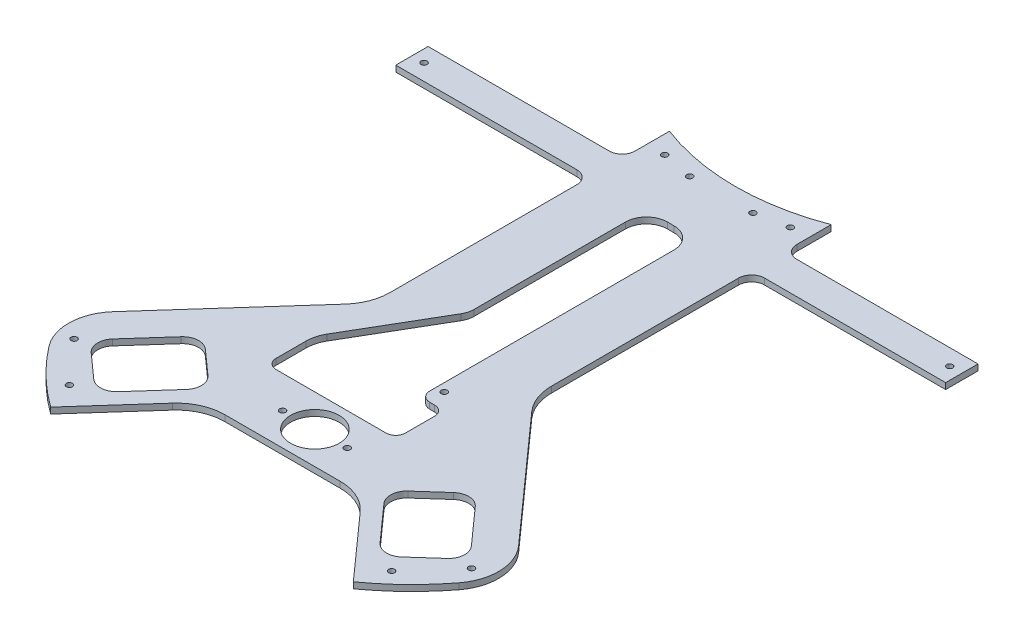
SolidWorks part; units mm, degrees
material "6063-T1"
ref_plane "Front Plane" through (0, 0, 0) normal (0, 0, 1) x (1, 0, 0)
ref_plane "Top Plane" through (0, 0, 0) normal (0, 1, 0) x (1, 0, 0)
ref_plane "Right Plane" through (0, 0, 0) normal (1, 0, 0) x (0, 0, -1)
sketch "Sketch1" plane through (0, 0, 0) normal (0, 1, 0) x (1, 0, 0)
  line L0 (-63.5, 31.75) -> (-178.5164, -97.0677)
  line L1 (-215.9, 31.75) -> (215.9, 31.75)
  line L2 (-215.9, 31.75) -> (-215.9, -31.75)
  line L3 (-215.9, -31.75) -> (215.9, -31.75)
  line L4 (215.9, 31.75) -> (215.9, -31.75)
  line L5 (-215.9, 31.75) -> (215.9, -31.75) construction
  line L6 (-215.9, -31.75) -> (215.9, 31.75) construction
  line L7 (63.5, 31.75) -> (-63.5, 31.75)
  line L8 (63.5, 31.75) -> (63.5, 292.608)
  line L9 (63.5, 292.608) -> (-63.5, 292.608)
  line L10 (-63.5, 31.75) -> (-63.5, 292.608)
  line L11 (0, -31.75) -> (-118.8264, -164.8348)
  line L12 (0, -31.75) -> (118.8264, -164.8348)
  line L13 (63.5, 31.75) -> (178.5164, -97.0677)
  line L14 (-62.3664, -101.6) -> (62.3664, -101.6)
  circle A1 centre (0, 0) radius 25.4 construction
  circle A2 centre (-25.4, 0) radius 2.3813
  circle A3 centre (25.4, 0) radius 2.3812
  circle A4 centre (0, 0) radius 203.2
  circle A5 centre (0, -76.2) radius 25.4 construction
  circle A6 centre (-25.4, -76.2) radius 2.3813
  circle A7 centre (25.4, -76.2) radius 2.3813
  point P0 (0, 0)
  dimension "D5" = 4.7625
  dimension "D6" = 4.7625
  dimension "D7" = 101.6
  dimension "D8" = 50.8
  dimension "D10" = 406.4
  dimension "D14" = 4.7625
  dimension "D15" = 4.7625
  dimension "D16" = 50.8
  dimension "D1" = 431.8
  dimension "D2" = 63.5
  dimension "D3" = 127
  dimension "D4" = 63.5
  dimension "D9" = 260.858
  dimension "D11" = 59.69
  dimension "D12" = 59.69
  dimension "D13" = 76.2
extrude "Boss-Extrude1" add sketch "Sketch1" along normal blind 4.7625 contours L10 L1 L8 L9 | L4 L1 L2 L3 A3 A2 | L0 A4 L11 L3 | L12 A4 L13 L3 | A4 L8 L9 L10 | L11 L14 L12 region at (0, 0, 3.2765) region at (0, 0, -115.8234) region at (-100.5416, 0, 84.5084) region at (0, 0, -246.176) region at (0, 0, 78.3341) region at (100.5416, 0, 84.5084)
sketch "Sketch2" plane through (0, 4.7625, 0) normal (0, 1, 0) x (1, 0, 0)
  line L0 (0, 292.608) -> (0, -101.6) construction
  line L1 (63.5, 292.608) -> (-63.5, 292.608) construction
  line L2 (-62.3664, -101.6) -> (62.3664, -101.6) construction
  circle A0 centre (25.4, 279.908) radius 2.3813
  circle A1 centre (50.8, 279.908) radius 2.3813
  circle A2 centre (-50.8, 279.908) radius 2.3813
  circle A3 centre (-25.4, 279.908) radius 2.3813
  dimension "D3" = 4.7625
  dimension "D4" = 4.7625
  dimension "D1" = 25.4
  dimension "D2" = 50.8
  dimension "D5" = 12.7
  dimension "D6" = 12.7
extrude "Cut-Extrude1" cut sketch "Sketch2" against normal through all
fillet "Fillet1" radius 38.1 4 edges at (63.5, 2.3813, -31.75) (-63.5, 2.3813, -31.75) (62.3664, 2.3813, 101.6) (-62.3664, 2.3813, 101.6)
sketch "Sketch4" plane through (0, 4.7625, 0) normal (0, 1, 0) x (1, 0, 0)
  line L0 (0, 292.608) -> (0, 0) construction
  line L1 (63.5, 292.608) -> (-63.5, 292.608) construction
  line L2 (0, 0) -> (0, -190.5) construction
  line L3 (0, 0) -> (-156.0485, -109.2663) construction
  circle A0 centre (0, 0) radius 190.5 construction
  circle A1 centre (-156.0485, -109.2663) radius 2.3813
  circle A2 centre (-126.4791, -142.4545) radius 2.3813
  circle A3 centre (126.4791, -142.4545) radius 2.3813
  circle A4 centre (156.0485, -109.2663) radius 2.3813
  dimension "D1" = 381
  dimension "D4" = 4.7625
  dimension "D5" = 4.7625
  dimension "D2" = 44.45
  dimension "D3" = 55
extrude "Cut-Extrude3" cut sketch "Sketch4" against normal through all
fillet "Fillet2" radius 38.1 2 edges at (178.5164, 2.3813, 97.0677) (-178.5164, 2.3813, 97.0677)
sketch "Sketch5" plane through (0, 4.7625, 0) normal (0, 1, 0) x (1, 0, 0)
  line L0 (-149.2765, -103.5959) -> (-111.3829, -137.4296)
  line L1 (-149.2765, -103.5959) -> (-106.9843, -56.229)
  line L2 (-111.3829, -137.4296) -> (-69.0908, -90.0627)
  line L3 (-106.9843, -56.229) -> (-69.0908, -90.0627)
  line L8 (-73.7278, -114.3247) -> (-118.8264, -164.8348) construction
  line L9 (0, 292.608) -> (0, -101.6) construction
  line L10 (63.5, 292.608) -> (-63.5, 292.608) construction
  line L11 (106.9843, -56.229) -> (69.0908, -90.0627)
  line L12 (111.3829, -137.4296) -> (69.0908, -90.0627)
  line L13 (149.2765, -103.5959) -> (106.9843, -56.229)
  line L14 (149.2765, -103.5959) -> (111.3829, -137.4296)
  line L15 (-45.3077, -101.6) -> (45.3077, -101.6) construction
  dimension "D1" = 50.8
  dimension "D2" = 12.7
  dimension "D3" = 63.5
  dimension "D4" = 25.4
extrude "Cut-Extrude4" cut sketch "Sketch5" against normal through all
fillet "Fillet3" radius 12.7 8 edges at (111.3829, 2.3813, 137.4296) (69.0908, 2.3813, 90.0627) (106.9843, 2.3813, 56.229) (149.2765, 2.3813, 103.5959) (-69.0908, 2.3813, 90.0627) (-106.9843, 2.3813, 56.229) (-149.2765, 2.3813, 103.5959) (-111.3829, 2.3813, 137.4296)
sketch "Sketch6" plane through (0, 4.7625, 0) normal (0, 1, 0) x (1, 0, 0)
  circle A0 centre (0, -76.2) radius 19.05
  dimension "D1" = 38.1
  dimension "D2" = 76.2
extrude "Cut-Extrude5" cut sketch "Sketch6" against normal through all
sketch "Sketch7" plane through (0, 4.7625, 0) normal (0, 1, 0) x (1, 0, 0)
  line L0 (-45.3077, -101.6) -> (45.3077, -101.6) construction
  line L1 (-19.05, 203.2) -> (19.05, 203.2)
  line L2 (-19.05, 203.2) -> (-19.05, -50.8)
  line L3 (-19.05, -50.8) -> (19.05, -50.8)
  line L4 (19.05, 203.2) -> (19.05, -50.8)
  line L5 (-19.05, 203.2) -> (19.05, -50.8) construction
  line L6 (-19.05, -50.8) -> (19.05, 203.2) construction
  point P0 (0, 76.2)
  dimension "D1" = 38.1
  dimension "D2" = 50.8
  dimension "D3" = 254
extrude "Cut-Extrude6" cut sketch "Sketch7" against normal through all
sketch "Sketch8" plane through (0, 4.7625, 0) normal (0, 1, 0) x (1, 0, 0)
  line L0 (-19.05, -50.8) -> (19.05, -50.8) construction
  line L1 (-63.5, -50.8) -> (38.1, -50.8)
  line L2 (-63.5, -50.8) -> (-63.5, -12.7)
  line L3 (-63.5, -12.7) -> (38.1, -12.7)
  line L4 (38.1, -50.8) -> (38.1, -12.7)
  dimension "D1" = 101.6
  dimension "D2" = 38.1
  dimension "D3" = 38.1
extrude "Cut-Extrude7" cut sketch "Sketch8" against normal through all
sketch "Sketch9" plane through (0, 4.7625, 0) normal (0, 1, 0) x (1, 0, 0)
  line L0 (-63.5, -12.7) -> (-19.05, 63.5)
  line L1 (-19.05, 203.2) -> (-19.05, -12.7) construction
  line L2 (-19.05, 63.5) -> (-19.05, -12.7)
  line L3 (-19.05, -12.7) -> (-63.5, -12.7)
  dimension "D1" = 76.2
extrude "Cut-Extrude8" cut sketch "Sketch9" against normal through all
fillet "Fillet4" radius 25.4 1 edges at (-63.5, 2.3813, 12.7)
fillet "Fillet5" radius 7.62 4 edges at (-63.5, 2.3813, 50.8) (38.1, 2.3813, 50.8) (38.1, 2.3813, 12.7) (19.05, 2.3813, 12.7)
fillet "Fillet8" radius 16.51 3 edges at (-19.05, 2.3813, -203.2) (19.05, 2.3813, -203.2) (-19.05, 2.3813, -63.5)
sketch "Sketch10" plane through (0, 4.7625, 0) normal (0, 1, 0) x (1, 0, 0)
  line L0 (0, 431.8) -> (0, 0) construction
  line L1 (0, 431.8) -> (-24.8652, 242.9298) construction
  line L2 (0, 431.8) -> (-49.305, 247.7911) construction
  circle A0 centre (0, 431.8) radius 177.8
  circle A1 centre (0, 431.8) radius 190.5 construction
  circle A2 centre (-49.305, 247.7911) radius 2.3812
  circle A3 centre (-24.8652, 242.9298) radius 2.3813
  circle A6 centre (24.8652, 242.9298) radius 2.3813
  circle A7 centre (49.305, 247.7911) radius 2.3812
  dimension "D1" = 355.6
  dimension "D3" = 381
  dimension "D4" = 4.7625
  dimension "D5" = 4.7625
  dimension "D6" = 7.5
  dimension "D7" = 15
  dimension "D2" = 431.8
extrude "Cut-Extrude9" cut sketch "Sketch10" against normal through all
sketch "Sketch11" plane through (0, 4.7625, 0) normal (0, 1, 0) x (1, 0, 0)
  line L1 (-215.9, 228.6) -> (215.9, 228.6)
  line L2 (-215.9, 228.6) -> (-215.9, 203.2)
  line L3 (-215.9, 203.2) -> (215.9, 203.2)
  line L4 (215.9, 228.6) -> (215.9, 203.2)
  line L5 (-215.9, 228.6) -> (215.9, 203.2) construction
  line L6 (-215.9, 203.2) -> (215.9, 228.6) construction
  point P0 (0, 215.9)
  point P5 (0, 0)
  dimension "D1" = 431.8
  dimension "D2" = 25.4
  dimension "D3" = 203.2
extrude "Boss-Extrude2" add sketch "Sketch11" against normal blind 4.7625
fillet "Fillet9" radius 10.16 4 edges at (63.5, 2.3813, -203.2) (63.5, 2.3813, -228.6) (-63.5, 2.3813, -203.2) (-63.5, 2.3813, -228.6)
sketch "Sketch12" plane through (0, 4.7625, 0) normal (0, 1, 0) x (1, 0, 0)
  line L0 (73.66, 203.2) -> (215.9, 203.2) construction
  line L1 (215.9, 203.2) -> (215.9, 228.6) construction
  line L2 (-215.9, 203.2) -> (-73.66, 203.2) construction
  line L3 (-215.9, 228.6) -> (-215.9, 203.2) construction
  circle A0 centre (-206.375, 215.9) radius 2.3813
  circle A1 centre (206.375, 215.9) radius 2.3813
  dimension "D1" = 4.7625
  dimension "D2" = 4.7625
  dimension "D3" = 12.7
  dimension "D4" = 9.525
  dimension "D5" = 12.7
  dimension "D6" = 9.525
extrude "Cut-Extrude10" cut sketch "Sketch12" against normal through all
